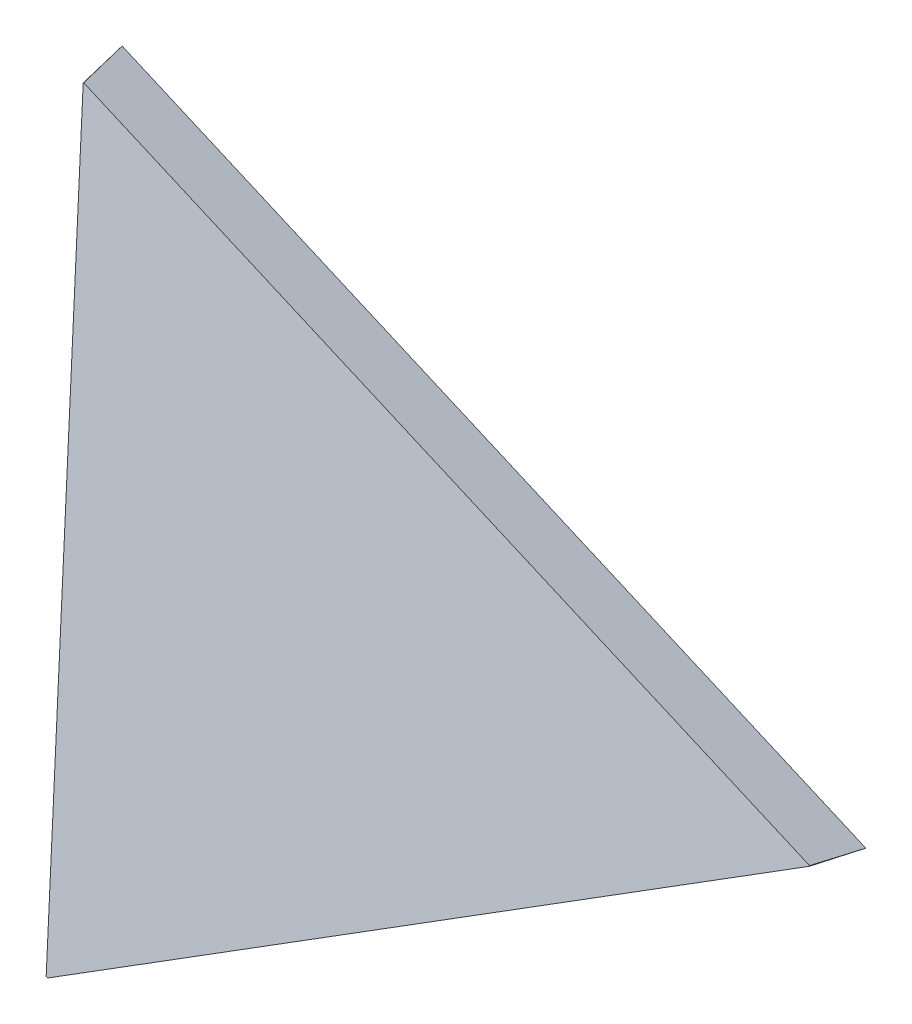
SolidWorks part; units mm, degrees
ref_plane "Front Plane" through (0, 0, 0) normal (0, 0, 1) x (1, 0, 0)
ref_plane "Top Plane" through (0, 0, 0) normal (0, 1, 0) x (1, 0, 0)
ref_plane "Right Plane" through (0, 0, 0) normal (1, 0, 0) x (0, 0, -1)
ref_plane "Plane1" through (228.2553, 263.4882, 1226.5423) normal (-0.179, -0.2066, -0.9619) x (-0.9838, 0.0376, 0.175)
sketch "Sketch1" plane through (231.9484, 267.7502, 1224.9394) normal (0.179, 0.2066, 0.9619) x (0.9837, -0.0188, -0.179)
  line L0 (-6114.5797, 916.6757) -> (-6017.0473, 65.8285)
  line L1 (-6017.0473, 65.8285) -> (-5261.2986, 468.69)
  line L2 (-5261.2986, 468.69) -> (-6114.5797, 916.6757)
extrude "Boss-Extrude1" add sketch "Sketch1" along normal blind 70
chamfer "Chamfer1" distance 70 angle 3.425 1 edges at (-5363.6228, 1067.0333, 2167.3249) first distance on face at (-5369.8881, 1059.801, 2133.6583)
chamfer "Chamfer2" distance 70 angle 5.44 2 edges at (-5731.1953, 874.641, 2277.0589) (-5309.8071, 648.8257, 2247.1501) first distance on face at (-5737.6262, 868.6427, 2243.1581) first distance on face at (-5314.9838, 642.1553, 2213.1602)
sketch "Sketch2" plane through (-1155.3196, -2341.4674, 1286.5847) normal (-0.3969, -0.8044, 0.442) x (0.9179, -0.3479, 0.1911)
  line L0 (-4919.3247, 2288.8483) -> (-4917.3139, 2288.2597)
  line L5 (-5745.7821, 2680.6261) -> (-4919.3247, 2288.8483) construction
  line L6 (-4938.4042, 2220.1734) -> (-4919.3247, 2288.8483) construction
  line L7 (-4917.3139, 2288.2597) -> (-4938.4042, 2220.1734)
  line L8 (-4938.4042, 2220.1734) -> (-4919.3247, 2288.8483)
  line L9 (-4917.3252, 2288.2611) -> (-4010.2664, 2171.0162) construction
  line L10 (-4917.3252, 2288.2611) -> (-4010.2664, 2171.0162) construction
  line L11 (-4918.41, 2288.2785) -> (-4428.307, 2279.8734) construction
  line L12 (-4917.3252, 2288.2611) -> (-4010.2664, 2171.0162) construction
extrude "Cut-Extrude1" cut sketch "Sketch2" along normal blind 10
sketch "Sketch3" plane through (-4820.8116, -663.5132, 188.265) normal (0.9899, 0.1362, -0.0387) x (-0.0383, -0.0053, -0.9993)
  line L0 (-2346.2264, 930.897) -> (-1894.2411, 2187.3962)
  line L5 (-1894.2411, 2187.3962) -> (-1814.9818, 1495.7704)
  line L6 (-1814.9818, 1495.7704) -> (-2346.2264, 930.897)
  line L7 (-1952.2515, 1508.6606) -> (-1981.6255, 2061.5196) construction
  line L8 (-2135.7634, 1239.5406) -> (-1952.2515, 1508.6606) construction
  line L9 (-1952.2515, 1508.6606) -> (-1981.6255, 2061.5196) construction
  line L10 (-2135.7634, 1239.5406) -> (-1952.2515, 1508.6606) construction
  line L16 (-1883.4204, 2313.8716) -> (-1981.5653, 2061.0922)
  line L17 (-1952.2747, 1509.0768) -> (-1883.4204, 2313.8716)
  line L18 (-1981.5653, 2061.0922) -> (-1952.2747, 1509.0768)
  line L19 (-1883.4204, 2313.8716) -> (-1981.5653, 2061.0922) construction
  line L20 (-1952.2747, 1509.0768) -> (-1883.4204, 2313.8716) construction
  line L21 (-1981.5653, 2061.0922) -> (-1952.2747, 1509.0768) construction
  point P2 (-1923.0377, 1551.5026)
  dimension "D1" = 0
extrude "Cut-Extrude2" cut sketch "Sketch3" along normal blind 10
sketch "Sketch4" plane through (-1646.0156, 3413.9262, 236.8367) normal (-0.4335, 0.899, 0.0624) x (0.9012, 0.4324, 0.03)
  line L1 (-4571.8662, -1241.3523) -> (-4859.2889, -1241.3523)
  line L2 (-4571.8662, -1241.3523) -> (-4571.8662, -2134.8706)
  line L3 (-4571.8662, -2134.8706) -> (-4859.2889, -2134.8706)
  line L4 (-4859.2889, -1241.3523) -> (-4859.2889, -2134.8706)
extrude "Cut-Extrude3" cut sketch "Sketch4" along normal blind 10
equation "\"D1@Boss-Extrude1\" = \"wall_thick@4Vcorrection.Assembly\""
equation "\"E\"= \"E@4Vcorrection.Assembly\""
equation "\"Thick\"= \"wall_thick@4Vcorrection.Assembly\""
equation "\"D1@Chamfer1\"=\"Thick\""
equation "\"D2@Chamfer1\"=\"E\""
equation "\"B\"= \"B@4Vcorrection.Assembly\""
equation "\"D2@Chamfer2\"=\"B\""
equation "\"D1@Chamfer2\"=\"Thick\""
